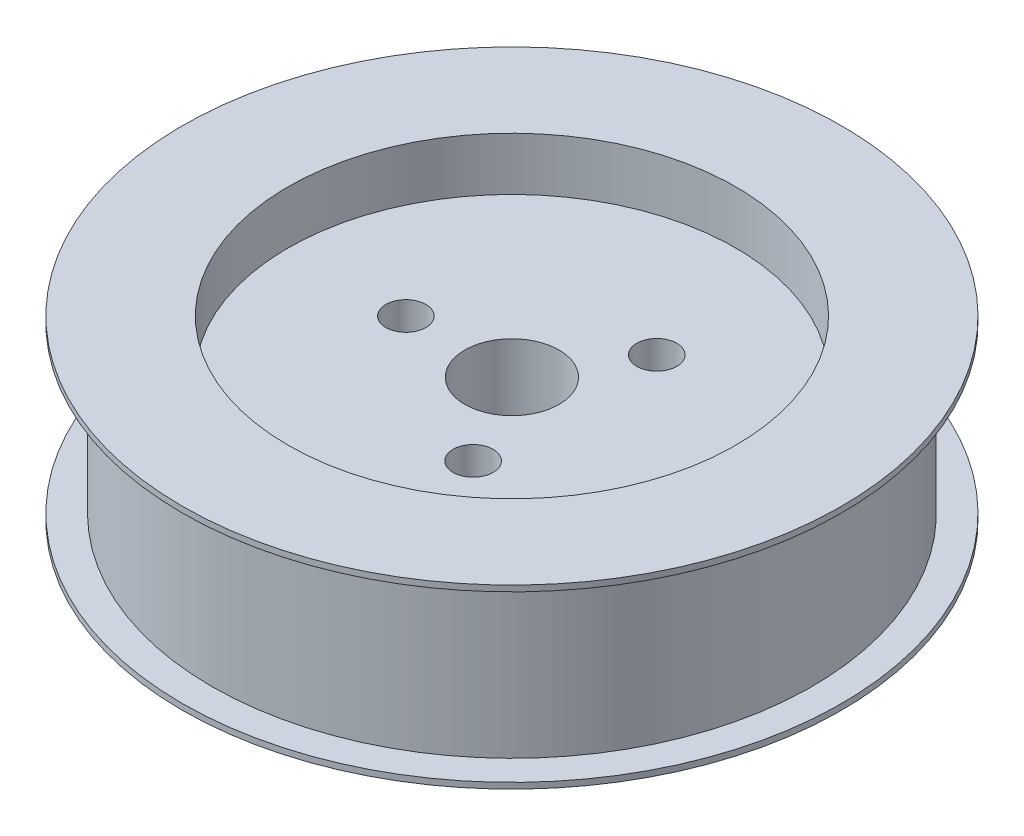
SolidWorks part; units mm, degrees
ref_plane "Alzado" through (0, 0, 0) normal (1, 0, 0) x (0, 1, 0)
ref_plane "Planta" through (0, 0, 0) normal (0, 0, 1) x (0, 1, 0)
ref_plane "Vista lateral" through (0, 0, 0) normal (0, 1, 0) x (-1, 0, 0)
sketch "Croquis1" plane through (0, 0, 0) normal (0, 1, 0) x (-1, 0, 0)
  circle A0 centre (0, 0) radius 25.47
  dimension "D1" = 50.94
extrude "Saliente-Extruir1" add sketch "Croquis1" along normal mid plane 15
sketch "Croquis2" plane through (0, 7.5, 0) normal (0, 1, 0) x (-1, 0, 0)
  circle A3 centre (0, 0) radius 27.97
  dimension "D1" = 55.94
extrude "Saliente-Extruir2" add sketch "Croquis2" against normal blind 0.5
extrude "Saliente-Extruir3" add sketch "Croquis2<2>" along normal blind 0.5 from surface starting at face at (0, -7.5, 25.47)
sketch "Croquis2<2>" plane through (0, 7.5, 0) normal (0, 1, 0) x (-1, 0, 0) same geometry as "Croquis2"
sketch "Croquis3" plane through (0, -7.5, 0) normal (0, 1, 0) x (-1, 0, 0)
  circle A0 centre (0, 0) radius 19
  dimension "D1" = 38
extrude "Saliente-Extruir4" add sketch "Croquis3" along normal blind 21
sketch "Croquis4" plane through (0, -7, 0) normal (0, 1, 0) x (-1, 0, 0)
  circle A0 centre (0, 0) radius 4
  dimension "D1" = 8
extrude "Cortar-Extruir1" cut sketch "Croquis4" against normal through all both and the other way through all
sketch "Croquis5" plane through (0, 13.5, 0) normal (0, 1, 0) x (-1, 0, 0)
  circle A0 centre (0, 0) radius 19
  circle A1 centre (0, 0) radius 19 construction
extrude "Cortar-Extruir2" cut sketch "Croquis5" against normal offset from surface (10.5 mm away) 3 up to plane "Vista lateral"
mirror "Simetría1" about plane through (0, 0, 0) normal (0, 1, 0) of "Cortar-Extruir2"
sketch "Croquis6" plane through (0, 7.5, 0) normal (0, 1, 0) x (-1, 0, 0)
  circle A0 centre (0, 0) radius 9 construction
  point P3 (9, 0)
  point P4 (-4.5, -7.7942)
  point P5 (0, 0)
  point P6 (0, 0)
  point P7 (-4.5, 7.7942)
  point P8 (0, 0)
  dimension "D1" = 18
  dimension "D2" = 3
hole_wizard "Taladro de margen para M31" positions "Croquis6" profile "Croquis7" hole size "M3" standard "Ansi Metric" end condition through all
sketch "Croquis7" plane through (0, 7.5, 0) normal (1, 0, 0) x (0, 0, 1)
  line L0 (0, 0) -> (0, 15)
  line L1 (0, 15) -> (1.7, 15)
  line L2 (1.7, 15) -> (1.7, 0)
  line L5 (1.7, 0) -> (0, 0)
  line L11 (0, -6.35) -> (0, 107.95) construction
  dimension "Diámetro de taladro hasta el siguiente" = 3.4
  dimension "Profundidad de taladro hasta el siguiente" = 15
equation "\"Dp\"= 50.94"
equation "\"D1@Croquis1\"=\"Dp\""
equation "\"Dm\"= 38"
equation "\"De\"= \"Dp\" + 5"
equation "\"F\"= 15"
equation "\"L\"= 21"
equation "\"D1@Croquis2\"=\"De\""
equation "\"D1@Saliente-Extruir1\"=\"F\""
equation "\"D1@Saliente-Extruir4\"=\"L\""
equation "\"deje\"=8"
equation "\"D1@Croquis4\"=\"deje\""
equation "\"D1@Croquis3\"=\"Dm\""
